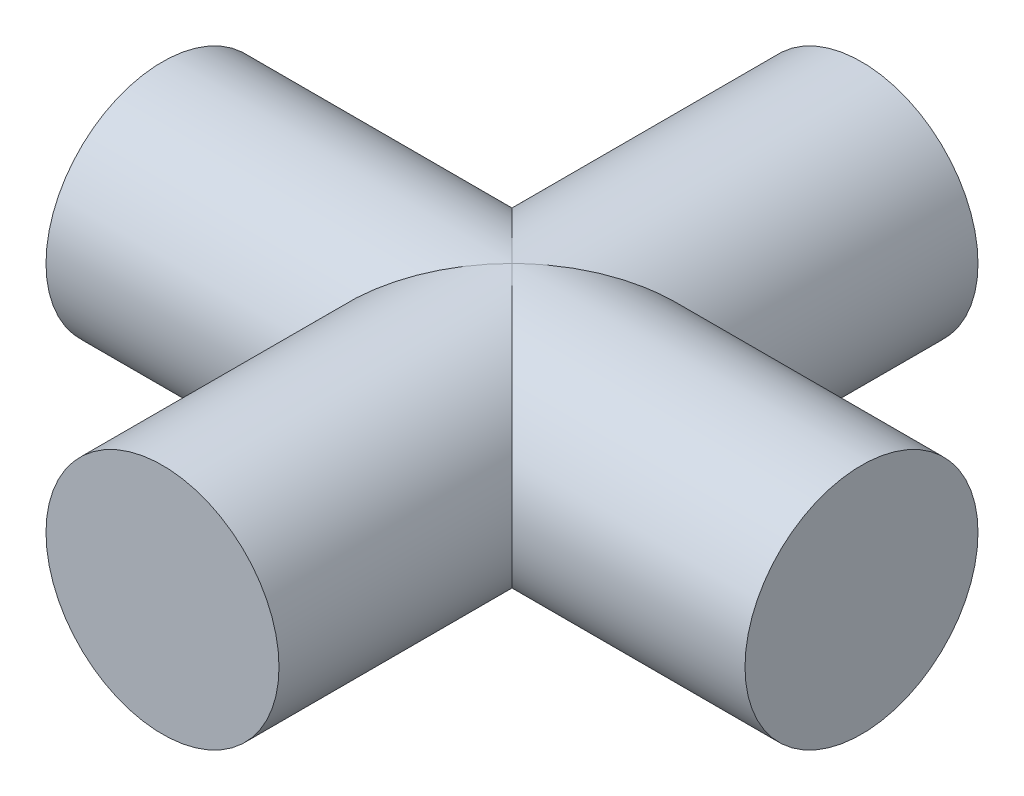
SolidWorks part; units mm, degrees
ref_plane "Front Plane" through (0, 0, 0) normal (0, 0, 1) x (1, 0, 0)
ref_plane "Top Plane" through (0, 0, 0) normal (0, 1, 0) x (1, 0, 0)
ref_plane "Right Plane" through (0, 0, 0) normal (1, 0, 0) x (0, 0, -1)
sketch "Sketch1" plane through (0, 0, 0) normal (0, 0, 1) x (1, 0, 0)
  circle A0 centre (0, 0) radius 10
  dimension "D1" = 20
extrude "Boss-Extrude1" add sketch "Sketch1" along normal blind 30 and the other way blind 30 contours A0
sketch "Sketch2" plane through (0, 0, 0) normal (1, 0, 0) x (0, 0, -1)
  line L0 (30, 10) -> (-30, 10) construction
  circle A0 centre (0, 0) radius 10
extrude "Boss-Extrude2" add sketch "Sketch2" along normal blind 30 and the other way blind 30
